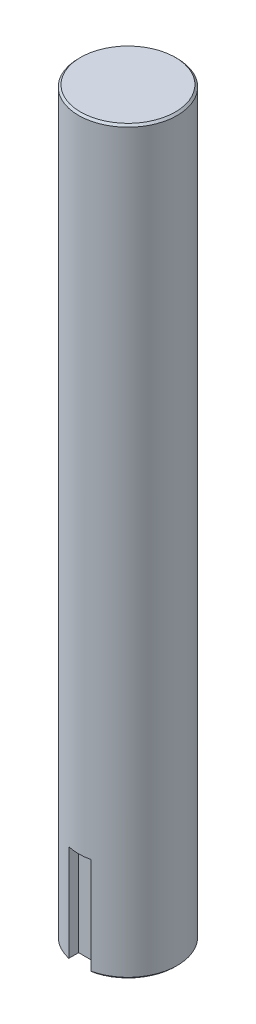
SolidWorks part; units mm, degrees
ref_plane "Front Plane" through (0, 0, 0) normal (0, 0, 1) x (1, 0, 0)
ref_plane "Top Plane" through (0, 0, 0) normal (0, 1, 0) x (1, 0, 0)
ref_plane "Right Plane" through (0, 0, 0) normal (1, 0, 0) x (0, 0, -1)
sketch "Sketch1" plane through (0, 0, 0) normal (0, 0, 1) x (1, 0, 0)
  line L1 (5, 75) -> (0, 75)
  line L2 (5, 75) -> (5, 0)
  line L3 (5, 0) -> (0, 0)
  line L4 (0, 75) -> (0, 0)
  line L5 (5, 75) -> (0, 0) construction
  line L6 (5, 0) -> (0, 75) construction
  point P0 (2.5, 37.5)
  dimension "D1" = 5
  dimension "D2" = 75
revolve "Revolve1" add sketch "Sketch1" angle 360 about L4
sketch "Sketch2" plane through (0, 0, 0) normal (0, -1, 0) x (1, 0, 0)
  line L1 (-1.125, 6.125) -> (1.125, 6.125)
  line L2 (-1.125, 6.125) -> (-1.125, 3.875)
  line L3 (-1.125, 3.875) -> (1.125, 3.875)
  line L4 (1.125, 6.125) -> (1.125, 3.875)
  line L5 (-1.125, 6.125) -> (1.125, 3.875) construction
  line L6 (-1.125, 3.875) -> (1.125, 6.125) construction
  circle A0 centre (0, 0) radius 5 construction
  point P0 (0, 5)
  point P7 (0, 0)
  dimension "D1" = 2.25
extrude "Cut-Extrude1" cut sketch "Sketch2" against normal blind 10
chamfer "Chamfer1" distance 0.2 angle 45 5 edges at (-5, 75, 0) (-1.125, 0, 4.3734) (0, 0, 3.875) (1.125, 0, 4.3734) (0, 0, -5)
ref_axis "Axis1" through (0, 0.2, 0) along (0, 1, 0)
